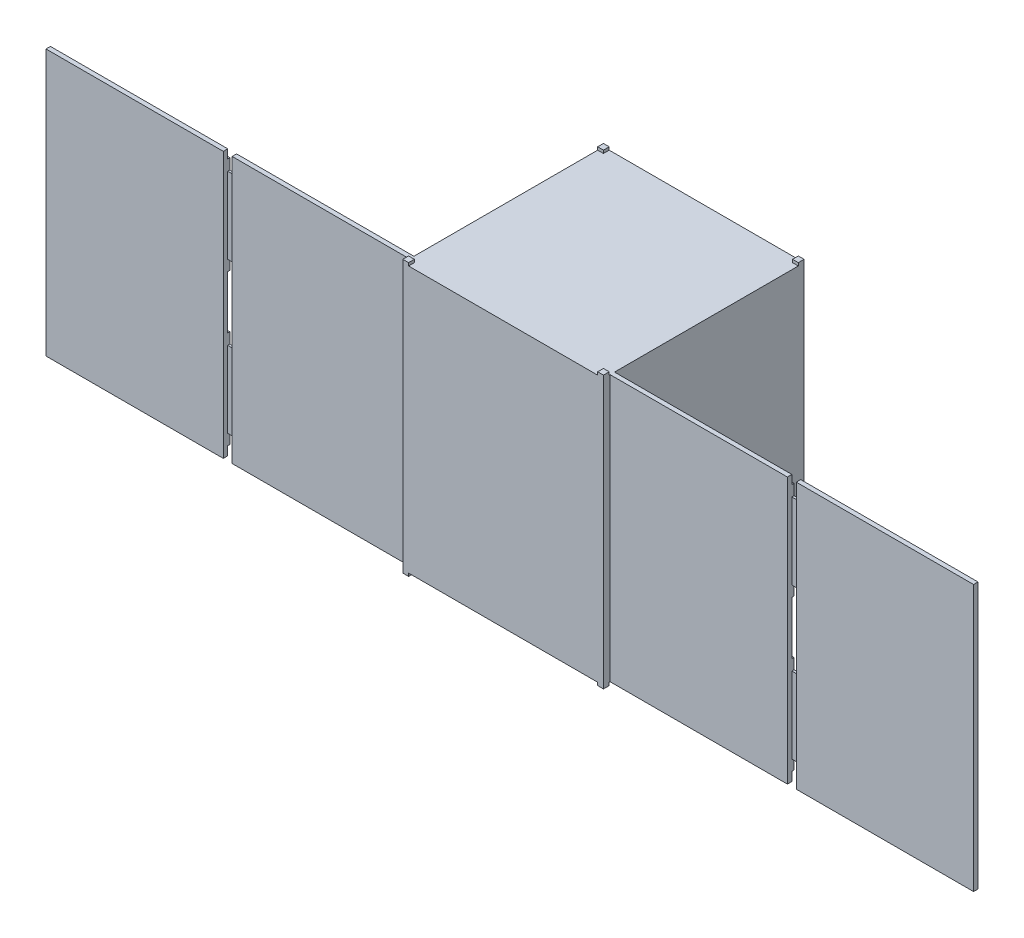
SolidWorks part; units mm, degrees
ref_plane "Piano frontale" through (0, 0, 0) normal (0, 0, 1) x (1, 0, 0)
ref_plane "Piano superiore" through (0, 0, 0) normal (0, 1, 0) x (1, 0, 0)
ref_plane "Piano destro" through (0, 0, 0) normal (1, 0, 0) x (0, 0, -1)
sketch "Schizzo2" plane through (0, 0, 0) normal (0, 1, 0) x (1, 0, 0)
  line L0 (-113.15, 106.65) -> (-113.15, -106.65)
  line L5 (-106.65, 113.15) -> (106.65, 113.15)
  line L6 (113.15, 106.65) -> (113.15, -106.65)
  line L7 (106.65, -113.15) -> (-106.65, -113.15)
  line L10 (-113.15, 106.65) -> (-106.65, 106.65)
  line L11 (-106.65, 113.15) -> (-106.65, 106.65)
  line L14 (-106.65, -113.15) -> (-106.65, -106.65)
  line L15 (-113.15, -106.65) -> (-106.65, -106.65)
  line L16 (113.15, -106.65) -> (106.65, -106.65)
  line L17 (106.65, -113.15) -> (106.65, -106.65)
  line L36 (106.65, 113.15) -> (106.65, 106.65)
  line L37 (106.65, 106.65) -> (113.15, 106.65)
extrude "Estrusione-Estrusione2" add sketch "Schizzo2" along normal blind 150 and the other way blind 150
sketch "Schizzo3" plane through (0, -150, 0) normal (0, -1, 0) x (1, 0, 0)
  line L1 (-106.65, 113.15) -> (-113.15, 113.15)
  line L2 (-106.65, 113.15) -> (-106.65, 106.65)
  line L3 (-106.65, 106.65) -> (-113.15, 106.65)
  line L4 (-113.15, 113.15) -> (-113.15, 106.65)
  line L5 (106.65, 113.15) -> (113.15, 113.15)
  line L6 (106.65, 113.15) -> (106.65, 106.65)
  line L7 (106.65, 106.65) -> (113.15, 106.65)
  line L8 (113.15, 113.15) -> (113.15, 106.65)
  line L9 (106.65, -106.65) -> (113.15, -106.65)
  line L10 (106.65, -106.65) -> (106.65, -113.15)
  line L11 (106.65, -113.15) -> (113.15, -113.15)
  line L12 (113.15, -106.65) -> (113.15, -113.15)
  line L13 (-106.65, -106.65) -> (-113.15, -106.65)
  line L14 (-106.65, -106.65) -> (-106.65, -113.15)
  line L15 (-106.65, -113.15) -> (-113.15, -113.15)
  line L16 (-113.15, -106.65) -> (-113.15, -113.15)
extrude "Estrusione-Estrusione3" add sketch "Schizzo3" along normal blind 3.3 and the other way blind 303.3
sketch "Schizzo4" plane through (0, 0, 113.15) normal (0, 0, 1) x (1, 0, 0)
  line L0 (-106.65, 153.3) -> (-106.65, -153.3)
  line L1 (-106.65, -153.3) -> (-113.15, -153.3)
  line L2 (-113.15, -153.3) -> (-113.15, 153.3)
  line L3 (-113.15, 153.3) -> (-106.65, 153.3)
  line L4 (106.65, 153.3) -> (113.15, 153.3)
  line L5 (113.15, 153.3) -> (113.15, -153.3)
  line L6 (113.15, -153.3) -> (106.65, -153.3)
  line L7 (106.65, -153.3) -> (106.65, 153.3)
sketch "Schizzo5" plane through (-113.15, 0, 0) normal (-1, 0, 0) x (0, 0, 1)
  line L1 (-106.65, 150) -> (106.65, 150) construction
  line L2 (105.65, 150) -> (100.65, 150)
  line L3 (105.65, 150) -> (105.65, -150)
  line L4 (105.65, -150) -> (100.65, -150)
  line L5 (100.65, 150) -> (100.65, -150)
  line L6 (-106.65, -150) -> (106.65, -150) construction
  line L7 (113.15, 153.3) -> (113.15, -153.3) construction
  dimension "D1" = 5
  dimension "D2" = 7.5
extrude "Estrusione-Estrusione4" add sketch "Schizzo5" along normal blind 200
sketch "Schizzo6" plane through (0, 0, 100.65) normal (0, 0, -1) x (-1, 0, 0)
  line L1 (313.15, 150) -> (113.15, 150) construction
  line L2 (298.15, 140) -> (338.15, 140)
  line L3 (298.15, 140) -> (298.15, 30)
  line L4 (298.15, 30) -> (338.15, 30)
  line L5 (338.15, 140) -> (338.15, 30)
  line L6 (313.15, 150) -> (313.15, -150) construction
  line L7 (0, 0) -> (409.2817, 0)
  line L8 (298.15, -30) -> (338.15, -30)
  line L9 (338.15, -140) -> (338.15, -30)
  line L10 (298.15, -140) -> (338.15, -140)
  line L11 (298.15, -140) -> (298.15, -30)
  line M8 (313.15, -150) -> (313.15, 150)
  dimension "D1" = 40
  dimension "D2" = 110
  dimension "D3" = 10
  dimension "D4" = 15
extrude "Estrusione-Estrusione5" add sketch "Schizzo6" along normal blind 2.5 contours L3 L4 L2 M8 | L5 L2 L4 M8 | L11 L10 L8 M8 | L10 L9 L8 M8 region at (-325.65, -85, 100.65) region at (-305.65, -85, 100.65) region at (-305.65, 85, 100.65) region at (-325.65, 85, 100.65)
sketch "Schizzo7" plane through (0, 0, 100.65) normal (0, 0, 1) x (1, 0, 0)
  line L2 (-313.15, 140) -> (-323.15, 140)
  line L3 (-313.15, 140) -> (-313.15, 128)
  line L4 (-313.15, 128) -> (-323.15, 128)
  line L5 (-323.15, 140) -> (-323.15, 128)
  line L12 (-313.15, 42) -> (-323.15, 42)
  line L13 (-323.15, 30) -> (-323.15, 42)
  line L14 (-313.15, 30) -> (-323.15, 30)
  line L15 (-313.15, 30) -> (-313.15, 42)
  line L16 (-313.15, -30) -> (-313.15, -42)
  line L17 (-313.15, -30) -> (-323.15, -30)
  line L18 (-323.15, -30) -> (-323.15, -42)
  line L19 (-313.15, -42) -> (-323.15, -42)
  line L20 (-313.15, -128) -> (-323.15, -128)
  line L21 (-323.15, -140) -> (-323.15, -128)
  line L22 (-313.15, -140) -> (-323.15, -140)
  line L23 (-313.15, -140) -> (-313.15, -128)
  dimension "D1" = 10
  dimension "D2" = 12
extrude "Taglio-Estrusione1" cut sketch "Schizzo7" against normal blind 2.5
sketch "Schizzo8" plane through (0, 0, 100.65) normal (0, 0, 1) x (1, 0, 0)
  line L2 (-323.15, 150) -> (-523.15, 150)
  line L3 (-323.15, 150) -> (-323.15, -150)
  line L4 (-323.15, -150) -> (-523.15, -150)
  line L5 (-523.15, 150) -> (-523.15, -150)
  line L6 (-313.15, -150) -> (-313.15, 150) construction
  dimension "D1" = 200
  dimension "D2" = 300
  dimension "D3" = 10
extrude "Estrusione-Estrusione6" add sketch "Schizzo8" along normal blind 5
sketch "Schizzo11" plane through (113.15, 0, 0) normal (1, 0, 0) x (0, 0, -1)
  line L1 (-100.65, 150) -> (-105.65, 150)
  line L2 (-100.65, 150) -> (-100.65, -150)
  line L3 (-100.65, -150) -> (-105.65, -150)
  line L4 (-105.65, 150) -> (-105.65, -150)
extrude "Estrusione-Estrusione8" add sketch "Schizzo11" along normal blind 200
sketch "Schizzo12" plane through (0, 0, 100.65) normal (0, 0, -1) x (-1, 0, 0)
  line L13 (-338.15, 140) -> (-298.15, 140)
  line L14 (-313.15, -150) -> (-313.15, 150) construction
  line L15 (-338.15, 140) -> (-338.15, 30)
  line L16 (-338.15, 30) -> (-298.15, 30)
  line L17 (-298.15, 140) -> (-298.15, 30)
  line L18 (-313.15, 150) -> (-113.15, 150) construction
  line L21 (-338.15, -30) -> (-298.15, -30)
  line L22 (-298.15, -140) -> (-298.15, -30)
  line L23 (-338.15, -140) -> (-298.15, -140)
  line L24 (-338.15, -140) -> (-338.15, -30)
  dimension "D2" = 10
  dimension "D9" = 40
  dimension "D10" = 110
  dimension "D11" = 15
extrude "Estrusione-Estrusione9" add sketch "Schizzo12" along normal blind 2.5
sketch "Schizzo13" plane through (0, 0, 98.15) normal (0, 0, -1) x (-1, 0, 0)
  line L1 (-313.15, 140) -> (-323.15, 140)
  line L2 (-313.15, 140) -> (-313.15, 128)
  line L3 (-313.15, 128) -> (-323.15, 128)
  line L4 (-323.15, 140) -> (-323.15, 128)
  line L6 (-313.15, 42) -> (-323.15, 42)
  line L7 (-323.15, 30) -> (-323.15, 42)
  line L8 (-313.15, 30) -> (-323.15, 30)
  line L9 (-313.15, 30) -> (-313.15, 42)
  line L12 (-313.15, -30) -> (-313.15, -42)
  line L13 (-313.15, -30) -> (-323.15, -30)
  line L14 (-323.15, -30) -> (-323.15, -42)
  line L15 (-313.15, -42) -> (-323.15, -42)
  line L16 (-313.15, -128) -> (-323.15, -128)
  line L17 (-323.15, -140) -> (-323.15, -128)
  line L18 (-313.15, -140) -> (-323.15, -140)
  line L19 (-313.15, -140) -> (-313.15, -128)
  dimension "D1" = 10
  dimension "D2" = 12
extrude "Taglio-Estrusione2" cut sketch "Schizzo13" against normal blind 2.5
sketch "Schizzo14" plane through (0, 0, 100.65) normal (0, 0, 1) x (1, 0, 0)
  line L2 (323.15, 150) -> (523.15, 150)
  line L3 (323.15, 150) -> (323.15, -150)
  line L4 (323.15, -150) -> (523.15, -150)
  line L5 (523.15, 150) -> (523.15, -150)
  line L8 (313.15, 150) -> (313.15, -150) construction
  dimension "D1" = 200
  dimension "D2" = 10
  dimension "300" = 300
extrude "Estrusione-Estrusione10" add sketch "Schizzo14" along normal blind 5 contours L2 L5 L4 L3
